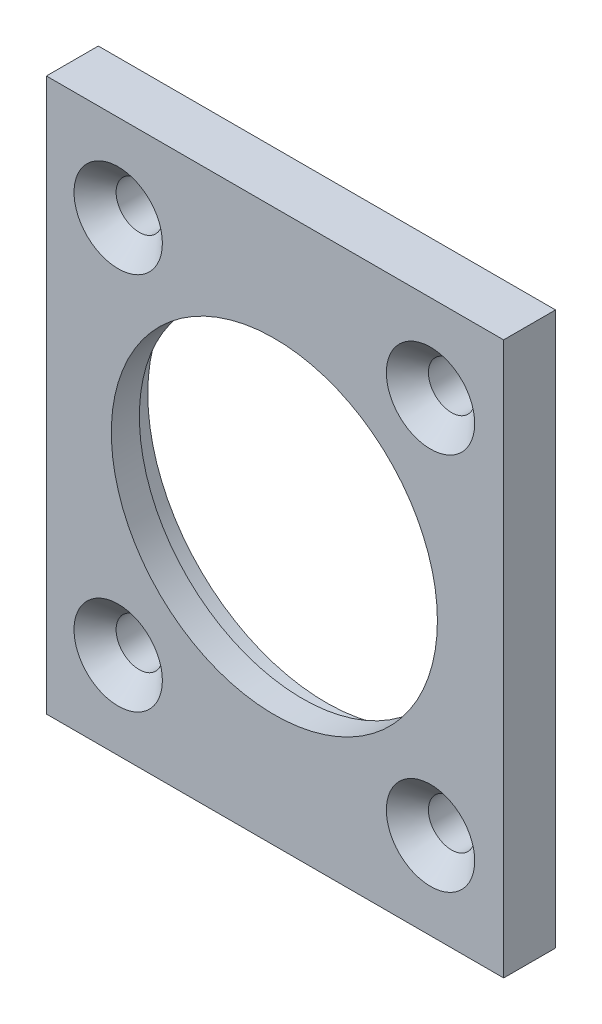
SolidWorks part; units mm, degrees
ref_plane "Front Plane" through (0, 0, 0) normal (0, 0, 1) x (1, 0, 0)
ref_plane "Top Plane" through (0, 0, 0) normal (0, 1, 0) x (1, 0, 0)
ref_plane "Right Plane" through (0, 0, 0) normal (1, 0, 0) x (0, 0, -1)
sketch "Sketch2" plane through (0, 0, 0) normal (0, 0, 1) x (1, 0, 0)
  line L3 (-16.4525, 19.898) -> (16.5456, 19.902) construction
  line L4 (16.5505, -19.3307) -> (16.5459, 18.0499) construction
  line L5 (-16.4475, -20.102) -> (-16.4522, 17.9012) construction
  line L6 (-16.2476, -19.702) -> (-16.2524, 19.698)
  line L7 (16.3505, -19.698) -> (16.3457, 19.702)
  line L8 (-16.2524, 19.698) -> (16.3457, 19.702)
  line L9 (16.3505, -19.3308) -> (16.3459, 18.0499) construction
  line L10 (-16.4524, 19.698) -> (16.5457, 19.702) construction
  line L11 (-16.2475, -20.102) -> (-16.2522, 17.9012) construction
  line L12 (-16.2476, -19.702) -> (16.3505, -19.698)
  line L13 (0, 0) -> (0.0466, 19.7) construction
  line L14 (0, 0) -> (0.0515, -19.7) construction
  line L15 (-16.4481, -15.102) -> (-16.4525, 19.898) construction
  line L16 (19.0437, 19.9024) -> (-18.9525, 19.8977) construction
  line L17 (16.55, -15.098) -> (16.5456, 19.902) construction
  circle A0 centre (0, 0) radius 11.425 construction
  circle A1 centre (0, 0) radius 11.425 construction
  circle A2 centre (0, 0) radius 11.625
  dimension "D5" = 39.4
  dimension "D6" = 32.5981
  dimension "D1" = 0.2
  dimension "D2" = 0.2
  dimension "D3" = 0.2
  dimension "D4" = 0.2
extrude "Boss-Extrude1" add sketch "Sketch2" against normal up to surface (2 mm away)
sketch "Sketch3" plane through (0, 0, -2) normal (0, 0, -1) x (-1, 0, 0)
  line L4 (-16.3505, -19.698) -> (16.2476, -19.702)
  line L5 (16.2476, -19.702) -> (16.2524, 19.698)
  line L7 (16.2476, -19.702) -> (16.2524, 19.698)
  line L8 (-16.3505, -19.698) -> (16.2476, -19.702)
  line L13 (16.2524, 19.698) -> (-16.3457, 19.702)
  line L15 (16.2524, 19.698) -> (-16.3457, 19.702)
  line L16 (-16.3457, 19.702) -> (-16.3505, -19.698)
  line L17 (-16.3457, 19.702) -> (-16.3505, -19.698)
  circle A0 centre (0, 0) radius 12.425 construction
  circle A1 centre (0, 0) radius 12.425 construction
  circle A2 centre (0, 0) radius 12.725
  dimension "D1" = 0.3
  dimension "D2" = 0
extrude "Boss-Extrude2" add sketch "Sketch3" along normal offset from surface (1.7 mm away) 0.3
sketch "Sketch5" plane through (0, 0, -3.7) normal (0, 0, -1) x (-1, 0, 0)
  line L0 (0, 0) -> (0, -0.9964) construction
  line L1 (0, 0) -> (-1.316, 0) construction
  line L2 (0, 0) -> (16.2476, -19.702) construction
  circle A1 centre (0, 0) radius 17.5 construction
  circle A4 centre (-11.134, -13.5012) radius 1.65
  circle A5 centre (-11.134, 13.5012) radius 1.65
  circle A6 centre (11.134, 13.5012) radius 1.65
  circle A7 centre (11.134, -13.5012) radius 1.65
  point P1 (11.2492, -13.4054)
  point P5 (11.1215, -13.4861)
  point P16 (0, 0)
  point P17 (8.937, -13.1681)
  point P18 (0, 0)
  point P20 (11.1786, -13.5553)
  point P21 (11.3151, -13.7208)
  dimension "D1" = 3.3
  dimension "D2" = 35
extrude "Cortar-Extruir1" cut sketch "Sketch5" against normal through all
chamfer "Chaflán1" distance 1.5 angle 45 4 edges at (-9.484, -13.5012, 0) (9.484, -13.5012, 0) (12.784, 13.5012, 0) (-12.784, 13.5012, 0)
